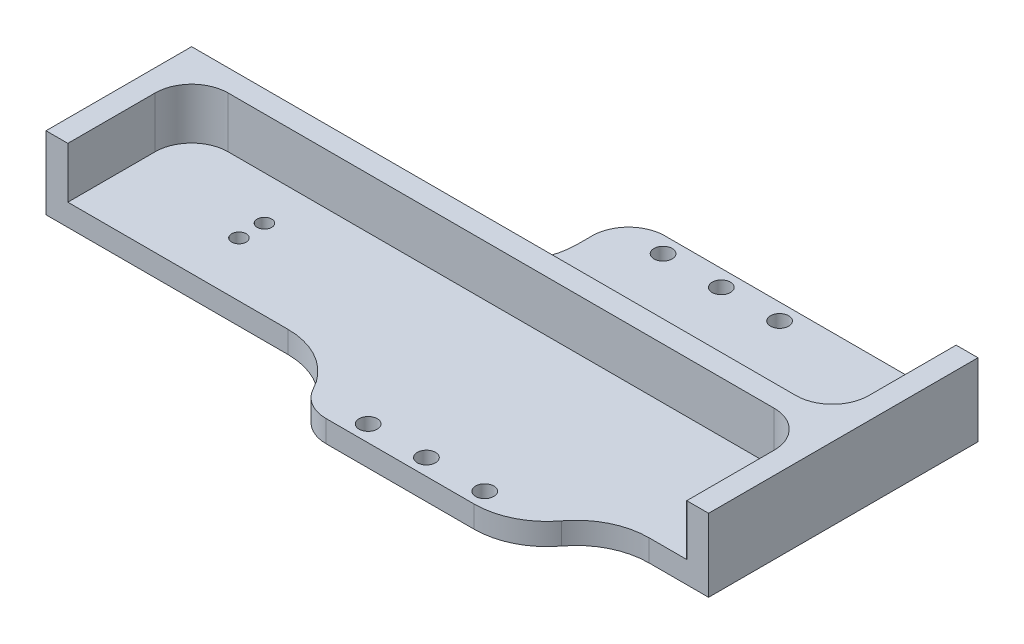
SolidWorks part; units mm, degrees
material "ABS"
ref_plane "Front Plane" through (0, 0, 0) normal (0, 0, 1) x (1, 0, 0)
ref_plane "Top Plane" through (0, 0, 0) normal (0, 1, 0) x (1, 0, 0)
ref_plane "Right Plane" through (0, 0, 0) normal (1, 0, 0) x (0, 0, -1)
sketch "Sketch1" plane through (0, 22.5, 0) normal (0, 1, 0) x (1, 0, 0)
  line L4 (24, -6) -> (54, -6)
  line L5 (54, -6) -> (54, 39)
  line L6 (54, 39) -> (24, 39)
  line L7 (24, 39) -> (24, -6)
  line L8 (24, -6) -> (54, -6)
  line L9 (54, -6) -> (54, 39)
  line L10 (54, 39) -> (24, 39)
  line L11 (24, 39) -> (24, -6)
  circle A12 centre (47, -3.75) radius 1.25 construction
  circle A13 centre (39, -3.75) radius 1.25 construction
  circle A14 centre (31, -3.75) radius 1.25 construction
  circle A15 centre (47, 36.75) radius 1.25 construction
  circle A16 centre (39, 36.75) radius 1.25 construction
  circle A17 centre (31, 36.75) radius 1.25 construction
  circle A18 centre (47, -3.75) radius 1.25
  circle A19 centre (39, -3.75) radius 1.25
  circle A20 centre (31, -3.75) radius 1.25
  circle A21 centre (47, 36.75) radius 1.25
  circle A22 centre (39, 36.75) radius 1.25
  circle A23 centre (31, 36.75) radius 1.25
  dimension "D1" = 0
extrude "LASER IF" add sketch "Sketch1" along normal blind 3
sketch "Sketch4" plane through (0, 21.5, 0) normal (0, 1, 0) x (1, 0, 0)
  line L0 (3.4641, 12.5) -> (2.9692, 9.0714)
  line L1 (-2.9692, 9.0714) -> (-3.4641, 12.5)
  circle A0 centre (0, 13) radius 1 construction
  circle A1 centre (0, 9.5) radius 1 construction
  circle A2 centre (0, 13) radius 1
  circle A3 centre (0, 9.5) radius 1
  arc A5 (-2.9692, 9.0714) -> (2.9692, 9.0714) centre (0, 9.5) ccw
  circle A6 centre (0, 13) radius 2.25 construction
  circle A8 centre (0, 9.5) radius 3 construction
  arc A10 (3.4641, 12.5) -> (-3.4641, 12.5) centre (0, 13) ccw
  dimension "D1" = 3.5
  dimension "D2" = 2
extrude "VLS IF TOP" add sketch "Sketch4" along normal blind 4 separate body
sketch "Sketch5" plane through (0, 25.5, 0) normal (0, 1, 0) x (1, 0, 0)
  line L0 (24, 39) -> (24, -6) construction
  line L1 (-19, 22) -> (24, 22)
  line L2 (-19, 22) -> (-19, 2)
  line L3 (-19, 2) -> (24, 2)
  line L4 (24, 22) -> (24, 2)
  line L5 (24, -6) -> (54, -6) construction
  line L7 (54, 39) -> (72, 39)
  line L8 (54, 39) -> (54, -6)
  line L9 (54, -6) -> (72, -6)
  line L10 (72, 39) -> (72, -6)
  circle A0 centre (0, 9.5) radius 1 construction
  circle A1 centre (0, 13) radius 1 construction
  circle A2 centre (0, 9.5) radius 1
  circle A3 centre (0, 13) radius 1
  dimension "D1" = 8
  dimension "D2" = 20
  dimension "D3" = 43
  dimension "D4" = 18
extrude "Boss-Extrude1" add sketch "Sketch5" against normal up to surface (3 mm away) up to face at (39, 22.5, -16.5)
fillet "Fillet1" radius 10 2 edges at (24, 24, -22) (24, 24, -2)
fillet "Fillet2" radius 5 2 edges at (24, 24, -39) (24, 24, 6)
sketch "Sketch6" plane through (0, 25.5, 0) normal (0, 1, 0) x (1, 0, 0)
  line L0 (-16, 2) -> (-19, 2)
  line L1 (-19, 2) -> (14.202, 2) construction
  line L2 (-19, 2) -> (-19, 22)
  line L3 (-19, 22) -> (69, 22)
  line L4 (69, 22) -> (69, 39)
  line L5 (72, 39) -> (29, 39) construction
  line L6 (69, 39) -> (72, 39)
  line L7 (72, 39) -> (72, 2)
  line L8 (72, 2) -> (69, 2)
  line L10 (69, 2) -> (69, 19)
  line L11 (69, 19) -> (-16, 19)
  line L12 (-16, 19) -> (-16, 2)
  point P8 (0, 0)
  dimension "D1" = 3
  dimension "D2" = 3
  dimension "D3" = 3
extrude "Boss-Extrude2" add sketch "Sketch6" along normal blind 7
fillet "Fillet3" radius 5 3 edges at (-16, 29, -19) (69, 29, -22) (69, 29, -19)
sketch "Sketch7" plane through (0, 25.5, 0) normal (0, 1, 0) x (1, 0, 0)
  line L0 (72, -6) -> (72, 2) construction
  line L1 (72, -6) -> (54, -6)
  line L2 (72, -6) -> (72, 2)
  line L3 (72, 2) -> (54, 2)
  line L4 (54, -6) -> (54, 2)
  circle A0 centre (39, -3.75) radius 1.25 construction
  point P5 (72, 2)
  point P10 (72, 2)
  dimension "D1" = 15
extrude "Cut-Extrude1" cut sketch "Sketch7" against normal through all
fillet "Fillet4" radius 10 1 edges at (54, 24, -2)
fillet "Fillet5" radius 10 1 edges at (54, 24, 6)
